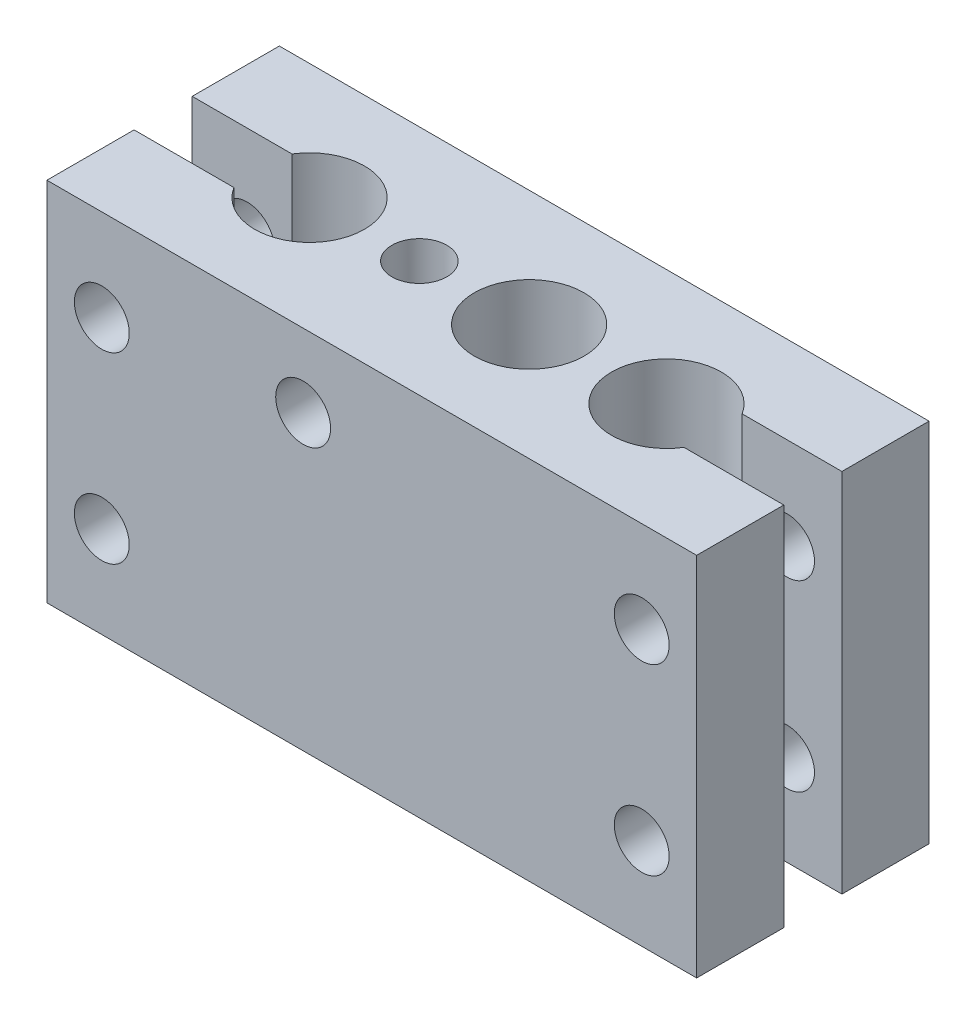
SolidWorks part; units mm, degrees
other "Markup1"
sketch "Sketch4" plane through (24, 12.7, 6.35) normal (0.1665, 0.6992, 0.6953) x (0.9508, 0.073, -0.3011)
material "6061 Alloy"
ref_plane "Front Plane" through (0, 0, 0) normal (0, 0, 1) x (1, 0, 0)
ref_plane "Top Plane" through (0, 0, 0) normal (0, 1, 0) x (1, 0, 0)
ref_plane "Right Plane" through (0, 0, 0) normal (1, 0, 0) x (0, 0, -1)
sketch "Sketch1" plane through (0, 0, 0) normal (0, 0, 1) x (1, 0, 0)
  line L1 (-17.75, -10) -> (17.75, -10)
  line L2 (-17.75, -10) -> (-17.75, 10)
  line L3 (-17.75, 10) -> (17.75, 10)
  line L4 (17.75, -10) -> (17.75, 10)
  line L5 (-17.75, -10) -> (17.75, 10) construction
  line L6 (-17.75, 10) -> (17.75, -10) construction
  point P0 (0, 0)
  dimension "D1" = 20
  dimension "D2" = 35.5
extrude "Boss-Extrude1" add sketch "Sketch1" along normal mid plane 12.7
sketch "Sketch2" plane through (0, 10, 0) normal (0, 1, 0) x (1, 0, 0)
  line L0 (17.75, -6.35) -> (17.75, 6.35) construction
  line L1 (0, -55) -> (0, 55) construction
  line L2 (-12.2956, -1.5875) -> (-12.2956, 1.5875)
  line L4 (-17.75, -1.5875) -> (-17.75, 1.5875)
  line L5 (12.2956, -1.5875) -> (17.75, -1.5875)
  line L6 (12.2956, -1.5875) -> (12.2956, 1.5875)
  line L7 (12.2956, 1.5875) -> (17.75, 1.5875)
  line L8 (17.75, -1.5875) -> (17.75, 1.5875)
  line L9 (-12.2956, 1.5875) -> (-17.75, 1.5875)
  line L10 (-12.2956, -1.5875) -> (-17.75, -1.5875)
  circle A0 centre (9.75, 0) radius 3
  circle A1 centre (2.25, 0) radius 3
  circle A2 centre (-3.75, 0) radius 1.5
  circle A3 centre (-9.75, 0) radius 3
  line M9 (17.75, -6.35) -> (17.75, 6.35)
  dimension "D1" = 6
  dimension "D2" = 6
  dimension "D3" = 3
  dimension "D4" = 3.175
  dimension "D5" = 8
  dimension "D6" = 7.5
  dimension "D7" = 6
extrude "Cut-Extrude1" cut sketch "Sketch2" against normal through all both and the other way through all contours A0 L5 L7 M9 | L6 A0 | A1 | A2 | L6 L7 L8 L5 | A3 | L2 L9 L4 L10 region at (15.175, 10, 0) region at (9.6523, 10, 0) region at (2.25, 10, 0) region at (-3.75, 10, 0)
sketch "Sketch3" plane through (0, 0, 6.35) normal (0, 0, 1) x (1, 0, 0)
  line L0 (14.75, -5) -> (14.75, 5) construction
  line L1 (17.75, -10) -> (17.75, 10) construction
  line L2 (17.75, 10) -> (-17.75, 10) construction
  line L4 (0, -55) -> (0, 55) construction
  circle A0 centre (14.75, 5) radius 1.5
  circle A1 centre (14.75, -5) radius 1.5
  circle A2 centre (-3.75, 6) radius 1.5
  circle A3 centre (-14.75, -5) radius 1.5
  circle A4 centre (-14.75, 5) radius 1.5
  point P6 (14.75, 0)
  dimension "D3" = 3
  dimension "D6" = 3
  dimension "D1" = 3
  dimension "D2" = 10
  dimension "D4" = 4
  dimension "D5" = 21.5
extrude "Cut-Extrude2" cut sketch "Sketch3" against normal through all both and the other way through all
